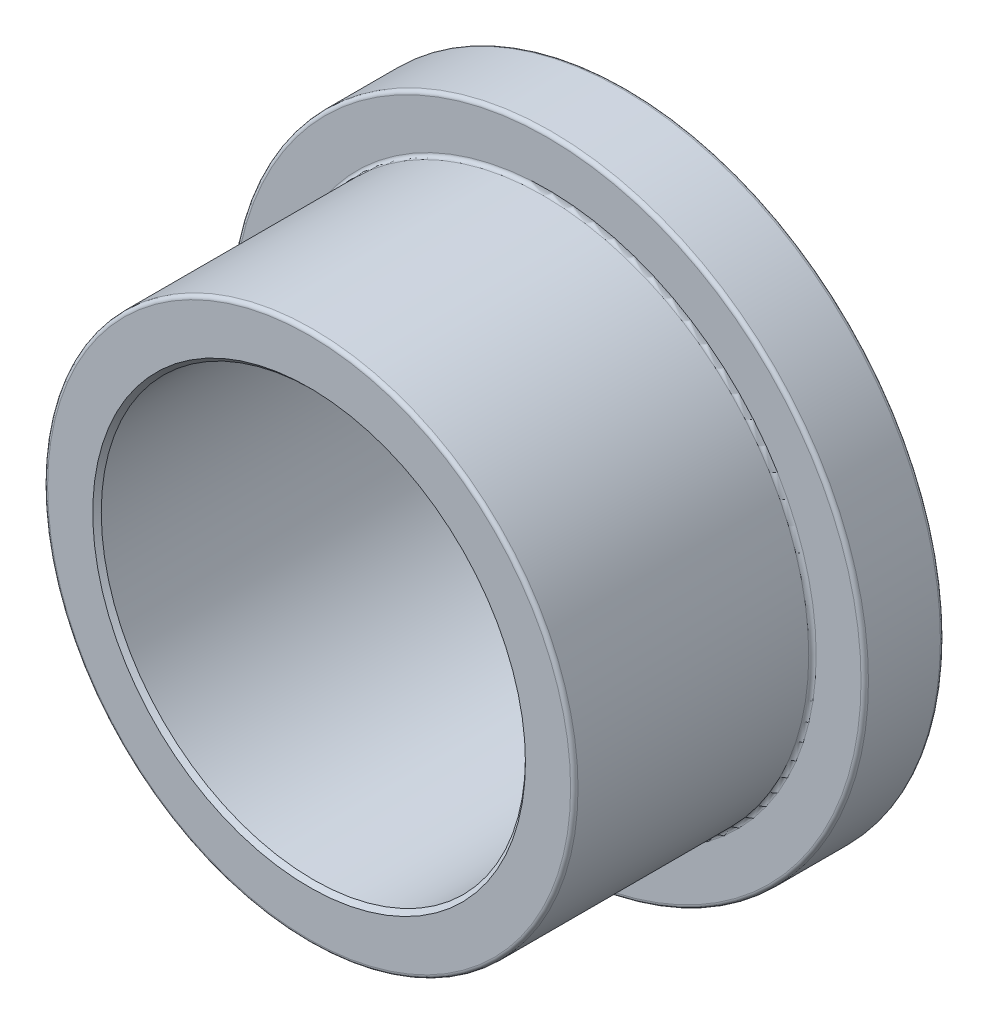
SolidWorks part; units mm, degrees
ref_plane "Front" through (0, 0, 0) normal (0, 0, 1) x (1, 0, 0)
ref_plane "Top" through (0, 0, 0) normal (0, 1, 0) x (1, 0, 0)
ref_plane "Right" through (0, 0, 0) normal (1, 0, 0) x (0, 0, -1)
sketch "Sketch1" plane through (0, 0, 0) normal (0, 0, 1) x (1, 0, 0)
  circle A0 centre (0, 0) radius 12.7254
  circle A1 centre (0, 0) radius 15.9131
  circle A2 centre (0, 0) radius 19.05
  point P5 (0, 19.05)
  point P6 (0, 15.9131)
  dimension "ID" = 25.4508
  dimension "OD" = 31.8262
  dimension "FlangeOD" = 38.1
sketch "Sketch2" plane through (0, 0, 0) normal (1, 0, 0) x (0, 0, -1)
  line L0 (0, 0) -> (-19.05, 0)
  point P3 (-4.7625, 0)
  point P4 (-19.05, 15.9131)
  dimension "Length" = 19.05
  dimension "FlangeThk" = 4.7625
sketch "Sketch3" plane through (0, 0, 0) normal (0, 0, 1) x (1, 0, 0)
  circle A0 centre (0, 0) radius 12.7254 construction
  circle A1 centre (0, 0) radius 15.9131 construction
  circle A2 centre (0, 0) radius 12.7254
  circle A3 centre (0, 0) radius 15.9131
extrude "Boss-Extrude1" add sketch "Sketch3" along normal up to vertex (19.05 mm away) up to point (0, 0, 19.05)
sketch "Sketch4" plane through (0, 0, 0) normal (0, 0, 1) x (1, 0, 0)
  circle A0 centre (0, 0) radius 19.05 construction
  circle A1 centre (0, 0) radius 15.9131 construction
  circle A2 centre (0, 0) radius 19.05
  circle A3 centre (0, 0) radius 15.9131
extrude "Boss-Extrude2" add sketch "Sketch4" along normal up to vertex (4.7625 mm away) up to point (0, 0, 4.7625)
chamfer "Chamfer1" distance 0.2545 angle 45 2 edges at (12.7254, 0, 0) (12.7254, 0, 19.05)
fillet "Fillet1" radius 0.2228 4 edges at (19.05, 0, 0) (19.05, 0, 4.7625) (15.9131, 0, 4.7625) (15.9131, 0, 19.05)
ref_axis "Center Axis 1" through (0, 0, 18.8272) along (0, 0, -1)
equation "\"D1@Chamfer1\"=\"ID@Sketch1\"*.01"
equation "\"D1@Fillet1\"=\"OD@Sketch1\"*.007"
